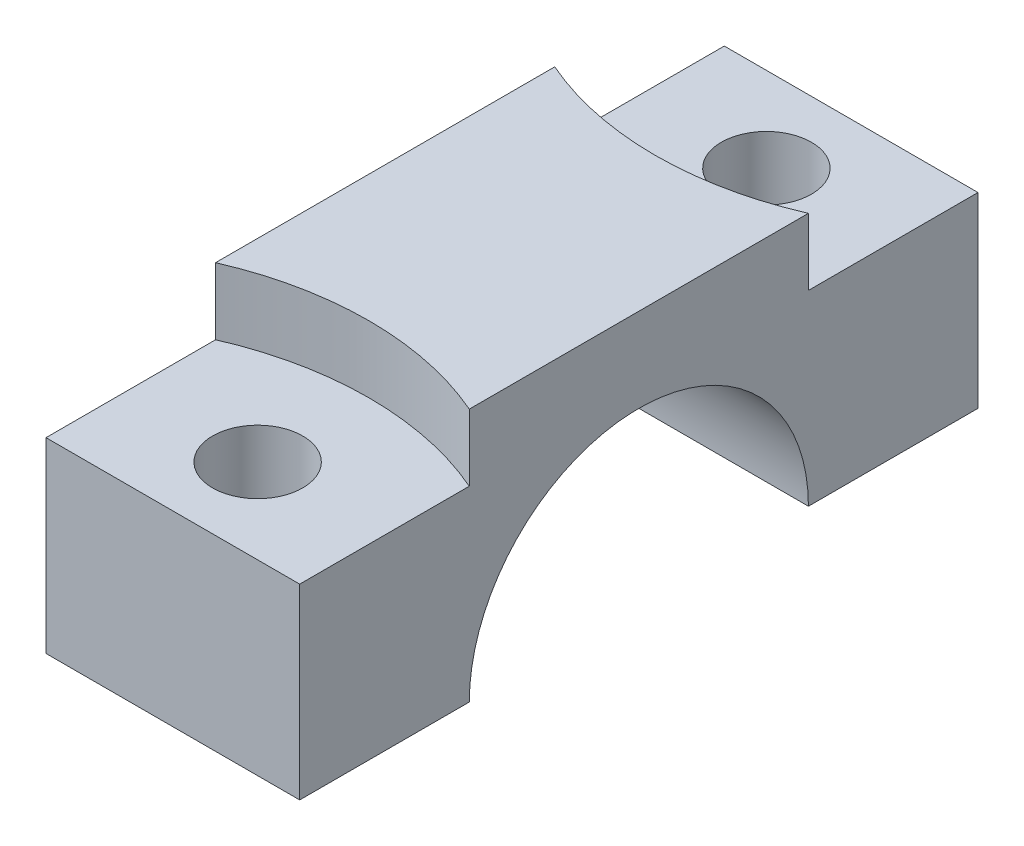
SolidWorks part; units mm, degrees
ref_plane "Front Plane" through (0, 0, 0) normal (0, 0, 1) x (1, 0, 0)
ref_plane "Top Plane" through (0, 0, 0) normal (0, 1, 0) x (1, 0, 0)
ref_plane "Right Plane" through (0, 0, 0) normal (1, 0, 0) x (0, 0, -1)
sketch "Sketch1" plane through (0, 0, 0) normal (0, 1, 0) x (1, 0, 0)
  line L0 (9.5, 64.1453) -> (9.5, -9.2612) construction
  line L1 (0, 0) -> (19, 0)
  line L2 (0, 0) -> (0, 50.8)
  line L3 (0, 50.8) -> (19, 50.8)
  line L4 (19, 0) -> (19, 50.8)
  line L9 (-16.5224, 25.4) -> (41.126, 25.4) construction
  circle A0 centre (9.5, 44.45) radius 3.375
  circle A1 centre (9.5, 6.35) radius 3.375
  arc A2 (0, 38.1) -> (19, 38.1) centre (9.5, 59.9109) ccw
  arc A3 (0, 12.7) -> (19, 12.7) centre (9.5, -9.1109) cw
  point P19 (0, 0)
  point P20 (0, 0)
  point P21 (0, 38.1)
  point P22 (0, 0)
  dimension "D3" = 6.75
  dimension "D7" = 23.79
  dimension "D1" = 50.8
  dimension "D2" = 19
  dimension "D4" = 9.5
  dimension "D5" = 25.4
  dimension "D6" = 6.35
  dimension "D8" = 25.4
extrude "Boss-Extrude1" add sketch "Sketch1" against normal blind 14 contours L2 A2 L4 L3 A0 | L2 L1 L4 L3 | A1 | A0 region at (0.2401, 0, -44.45)
extrude "Boss-Extrude2" add sketch "Sketch1<3>" along normal blind 5 contours L2 A3 L4 A2 region at (9.5, 0, -25.4)
sketch "Sketch1<3>" plane through (0, 0, 0) normal (0, 1, 0) x (1, 0, 0) same geometry as "Sketch1"
sketch "Sketch2" plane through (19, 0, 0) normal (1, 0, 0) x (0, 0, -1)
  line L0 (25.4, 12.7323) -> (25.4, -19.8209) construction
  line L1 (0, -14) -> (50.8, -14) construction
  line L2 (0, -14) -> (0, 0) construction
  circle A0 centre (25.4, -14) radius 12.7
  point P2 (25.4, -14)
  point P10 (0, 0)
  dimension "D3" = 25.4
  dimension "D1" = 25.4
extrude "Cut-Extrude1" cut sketch "Sketch2" against normal through all
